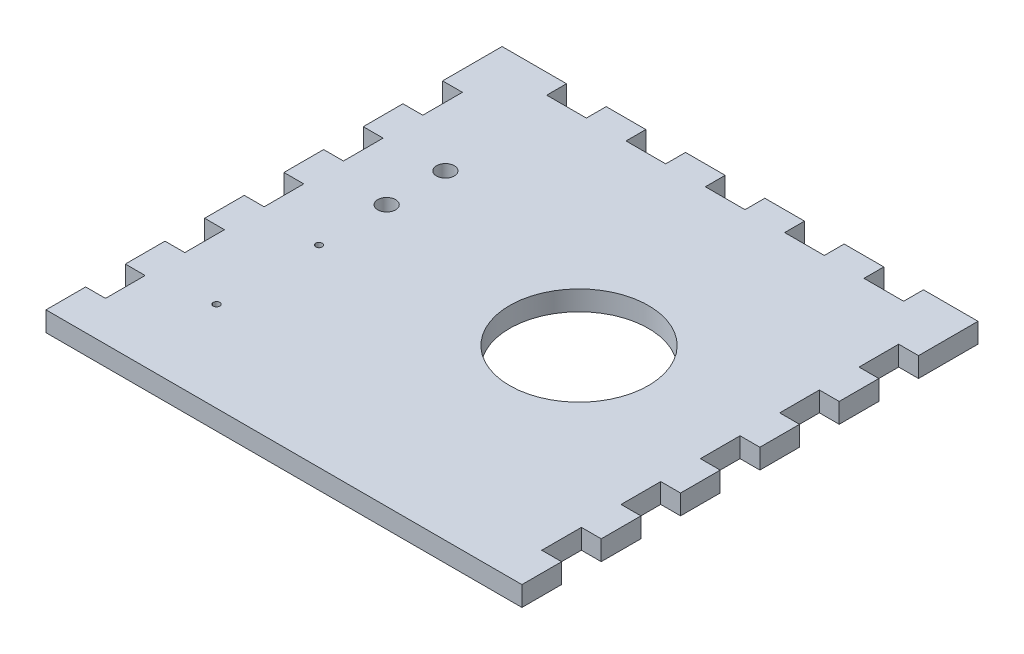
SolidWorks part; units mm, degrees
ref_plane "Front Plane" through (0, 0, 0) normal (0, 0, 1) x (1, 0, 0)
ref_plane "Top Plane" through (0, 0, 0) normal (0, 1, 0) x (1, 0, 0)
ref_plane "Right Plane" through (0, 0, 0) normal (1, 0, 0) x (0, 0, -1)
sketch "Sketch1" plane through (0, 0, 0) normal (0, 1, 0) x (1, 0, 0)
  line L1 (-139.7, -139.7) -> (139.7, -139.7)
  line L2 (-139.7, -139.7) -> (-139.7, 139.7)
  line L3 (-139.7, 139.7) -> (139.7, 139.7)
  line L4 (139.7, -139.7) -> (139.7, 139.7)
  line L5 (-139.7, -139.7) -> (139.7, 139.7) construction
  line L6 (-139.7, 139.7) -> (139.7, -139.7) construction
  point P0 (0, 0)
  dimension "D1" = 279.4
  dimension "D2" = 279.4
extrude "Boss-Extrude1" add sketch "Sketch1" along normal blind 12.7
sketch "Sketch2" plane through (139.7, 0, 0) normal (1, 0, 0) x (0, 0, -1)
  line L0 (-139.7, 12.7) -> (139.7, 12.7) construction
  line L1 (-139.7, 0) -> (-114.3, 0)
  line L2 (-139.7, 0) -> (-139.7, 12.7)
  line L3 (-139.7, 12.7) -> (-114.3, 12.7)
  line L4 (-114.3, 0) -> (-114.3, 12.7)
  dimension "D1" = 25.4
extrude "Boss-Extrude2" add sketch "Sketch2" along normal blind 12.7
pattern_linear "LPattern1" count 6 spacing 50.8 along (0, 0, -1) of "Boss-Extrude2"
mirror "Mirror1" about plane through (0, 0, 0) normal (1, 0, 0) of "LPattern1"
sketch "Sketch3" plane through (0, 0, -139.7) normal (0, 0, -1) x (-1, 0, 0)
  line L0 (-152.4, 12.7) -> (152.4, 12.7) construction
  line L1 (-142.875, 12.7) -> (-117.475, 12.7)
  line L2 (-142.875, 12.7) -> (-142.875, 0)
  line L3 (-142.875, 0) -> (-117.475, 0)
  line L4 (-117.475, 12.7) -> (-117.475, 0)
  line L5 (-152.4, 0) -> (152.4, 0) construction
  line L6 (-152.4, 0) -> (-152.4, 12.7) construction
  dimension "D1" = 9.525
  dimension "D2" = 25.4
extrude "Boss-Extrude3" add sketch "Sketch3" along normal blind 12.7
pattern_linear "LPattern2" count 6 spacing 50.8 along (-1, 0, 0) of "Boss-Extrude3"
sketch "Sketch5" plane through (0, 0, -139.7) normal (0, 0, -1) x (-1, 0, 0)
  line L6 (160.655, 0) -> (-160.655, 0) construction
  line L7 (-152.4, 12.7) -> (-135.3964, 12.7)
  line L8 (-152.4, 12.7) -> (-152.4, 0)
  line L9 (-152.4, 0) -> (-135.3964, 0)
  line L10 (-135.3964, 12.7) -> (-135.3964, 0)
extrude "Boss-Extrude4" add sketch "Sketch5" along normal blind 12.7
mirror "Mirror2" about plane through (0, 0, 0) normal (1, 0, 0) of "Boss-Extrude4"
sketch "Sketch6" plane through (0, 12.7, 0) normal (0, 1, 0) x (1, 0, 0)
  line L0 (66.675, 139.7) -> (41.275, 139.7) construction
  line L1 (139.7, -12.7) -> (139.7, 12.7) construction
  circle A0 centre (38.1, 11.176) radius 44.45
  dimension "D1" = 128.524
  dimension "D2" = 101.6
extrude "Cut-Extrude1" cut sketch "Sketch6" against normal through all
sketch "Sketch7" plane through (0, 12.7, 0) normal (0, 1, 0) x (1, 0, 0)
  line L0 (-139.7, 63.5) -> (-139.7, 38.1) construction
  line L1 (-139.7, 114.3) -> (-139.7, 88.9) construction
  line L2 (-85.725, 139.7) -> (-111.125, 139.7) construction
  circle A0 centre (-101.6, 65.278) radius 5.715
  circle A1 centre (-101.6, 27.686) radius 5.715
  dimension "D1" = 11.43
  dimension "D2" = 11.43
  dimension "D3" = 38.1
  dimension "D4" = 38.1
  dimension "D5" = 37.592
  dimension "D6" = 74.422
extrude "Cut-Extrude2" cut sketch "Sketch7" against normal through all
sketch "Sketch8" plane through (0, 12.7, 0) normal (0, 1, 0) x (1, 0, 0)
  circle A0 centre (-100.9, -81.9861) radius 2.1 construction
  circle A1 centre (-100.9, -81.9861) radius 2.1
  circle A2 centre (-100.9, -16.3789) radius 2.1 construction
  circle A3 centre (-100.9, -16.3789) radius 2.1
extrude "Cut-Extrude3" cut sketch "Sketch8" against normal through all
sketch "Sketch9" plane through (0, 12.7, 0) normal (0, 1, 0) x (1, 0, 0)
  circle A0 centre (80.3243, 112.3205) radius 12.1113
  circle A1 centre (80.3243, 112.3205) radius 15.9341
  circle A2 centre (118.6769, 96.3864) radius 9.3629
  circle A3 centre (118.6769, 96.3864) radius 13.2353
